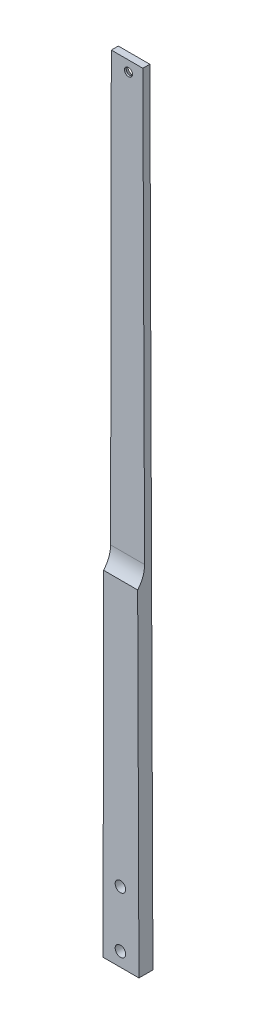
SolidWorks part; units mm, degrees
material "6061-T6 (SS)"
ref_plane "XY" through (0, 0, 0) normal (0, 0, 1) x (1, 0, 0)
ref_plane "XZ" through (0, 0, 0) normal (0, 1, 0) x (1, 0, 0)
ref_plane "YZ" through (0, 0, 0) normal (1, 0, 0) x (0, 0, -1)
ref_axis "X" through (-34.925, 0, 0) along (1, 0, 0)
ref_axis "Y" through (0, -53.3373, 0) along (0, 1, 0)
ref_axis "Z" through (0, 0, 6.6675) along (0, 0, -1)
sketch "Sketch1" plane through (0, 0, 0) normal (0, 0, 1) x (1, 0, 0)
  line L0 (-5.3354, 399.996) -> (10.3597, 399.996)
  line B0 (9.0464, 399.996) -> (-5.2871, 399.996)
  arc B1 (10.4977, 29.9643) -> (-5.8638, 31.2038) centre (0, 0) ccw
  spline B2 degree 3 poles (-5.2871, 399.996) (-5.392, 338.6022) (-5.5295, 254.0955) (-5.7181, 131.1648) (-5.8086, 69.6278) (-5.8638, 31.2038) knots 0 0 0 0 0.499418 0.687434 1 1 1 1
  spline B3 degree 3 poles (10.4977, 29.9643) (10.3579, 67.799) (10.0202, 157.8026) (9.6677, 247.8061) (9.323, 333.3153) (9.1861, 366.6557) (9.0464, 399.996) knots 0 0 0 0 0.306741 0.729696 0.729696 1 1 1 1
sketch_block_instance "Block2-3"
sketch_block "Block2"
sketch "Sketch2" plane through (0, 0, 0) normal (0, 0, 1) x (1, 0, 0)
  line L5 (-5.3354, 399.996) -> (10.3597, 399.996) construction
  line L6 (-5.2871, 399.996) -> (9.0464, 399.996)
  arc A1 (11.1829, 29.7154) -> (-6.1429, 31.1501) centre (0, 0) ccw construction
  arc A2 (10.4977, 29.9643) -> (-5.8638, 31.2038) centre (0, 0) ccw construction
  arc A3 (10.4977, 29.9643) -> (-5.8638, 31.2038) centre (0, 0) ccw
  spline S2 degree 3 poles (23.5275, -2969.9802) (16.0548, -1932.1789) (13.9359, -842.1823) (9.6677, 247.8061) (5.2912, 1333.2834) (-1.242, 2366.5824) (-18.9106, 3399.8182) knots -8.107291 -8.107291 -8.107291 -8.107291 0.306741 0.729696 0.729696 9.107159 9.107159 9.107159 9.107159 only from (10.4977, 29.9643) to (9.0464, 399.996) construction
  spline S3 degree 3 poles (7.1386, 3399.9286) (-1.0288, 2338.5658) (-3.9953, 1254.0783) (-7.2523, -868.8146) (-7.7134, -1930.3327) (-10.8836, -2968.7314) knots -8.134522 -8.134522 -8.134522 -8.134522 0.499418 0.687434 9.134495 9.134495 9.134495 9.134495 only from (-5.2871, 399.996) to (-5.8638, 31.2038) construction
  spline S8 degree 3 poles (10.4977, 29.9643) (10.3579, 67.799) (10.0202, 157.8026) (9.6677, 247.8061) (9.323, 333.3153) (9.1861, 366.6557) (9.0464, 399.996) knots 0 0 0 0 0.306741 0.729696 0.729696 1 1 1 1
  spline S9 degree 3 poles (-5.2871, 399.996) (-5.392, 338.6022) (-5.5295, 254.0955) (-5.7181, 131.1648) (-5.8086, 69.6278) (-5.8638, 31.2038) knots 0 0 0 0 0.499418 0.687434 1 1 1 1
  point P0 (0, 0)
extrude "Boss-Extrude1" add sketch "Sketch2" along normal blind 6.35
sketch "Sketch3" plane through (0, 0, 0) normal (0, 0, 1) x (1, 0, 0)
  line L0 (0, 0) -> (2.032, 0) construction
  line L1 (-9.398, 0) -> (13.462, 0)
  line L2 (-9.398, 0) -> (-9.398, 44.45)
  line L3 (-9.398, 44.45) -> (13.462, 44.45)
  line L4 (13.462, 0) -> (13.462, 44.45)
  line L9 (2.032, 0) -> (2.032, 44.45) construction
  line L11 (13.462, 44.45) -> (-9.398, 44.45) construction
  circle A0 centre (0, 0) radius 31.75 construction
  dimension "D1" = 63.5
  dimension "D2" = 44.45
  dimension "D3" = 2.032
  dimension "D6" = 22.86
extrude "Cut-Extrude2" cut sketch "Sketch3" against normal through all and the other way through all
hole_wizard "3/16 (0.1875) Dowel Hole1" positions "Sketch4" profile "Sketch5" hole size "3/16" standard "ANSI Inch"
sketch "Sketch4" plane through (0, 0, 6.35) normal (0, 0, 1) x (1, 0, 0)
  line L0 (2.032, 44.45) -> (2.032, 50.8) construction
  line L2 (2.032, 50.8) -> (2.032, 76.2) construction
  line L4 (10.4441, 44.45) -> (-5.8447, 44.45) construction
  point P0 (2.032, 50.8)
  point P2 (2.032, 76.2)
  dimension "D1" = 6.35
  dimension "D2" = 25.4
  dimension "D3" = 2.032
sketch "Sketch5" plane through (2.032, 50.8, 6.35) normal (1, 0, 0) x (0, -1, 0)
  line L0 (0, 0) -> (0, 12.0988)
  line L1 (0, 12.0988) -> (2.3812, 10.668)
  line L2 (2.3812, 10.668) -> (2.3812, 0)
  line L5 (2.3812, 0) -> (0, 0)
  line L10 (0, 12.0988) -> (-2.3813, 10.668) construction
  line L11 (0, -6.35) -> (0, 107.95) construction
  dimension "Hole Dia." = 4.7625
  dimension "Hole Depth" = 10.668
  dimension "Drill Angle" = 118
hole_wizard "CSK for #6 Flat Head Socket Cap Screw1" positions "Sketch6" profile "Sketch7" countersink size "#6" standard "ANSI Inch" end condition through all
sketch "Sketch6" plane through (0, 0, 0) normal (0, 0, -1) x (-1, 0, 0)
  line L0 (-2.5122, 395.2335) -> (-2.5122, 399.996) construction
  line L1 (5.3354, 399.996) -> (-10.3597, 399.996) construction
  point P0 (-2.5122, 395.2335)
  dimension "D1" = 4.7625
sketch "Sketch7" plane through (2.5122, 395.2335, 0) normal (1, 0, 0) x (0, 1, 0)
  line L0 (0, 0) -> (0, 6.35)
  line L1 (0, 6.35) -> (1.8288, 6.35)
  line L2 (1.8288, 6.35) -> (1.8288, 2.3814)
  line L3 (1.8288, 2.3814) -> (3.8989, 0)
  line L5 (3.8989, 0) -> (0, 0)
  line L6 (-1.8288, 2.3814) -> (-3.8989, 0) construction
  line L11 (0, -6.35) -> (0, 107.95) construction
  dimension "Thru Hole Dia." = 3.6576
  dimension "Thru Hole Depth" = 6.35
  dimension "Near C'Sink Dia." = 7.7978
  dimension "Near C'Sink Angle" = 82
sketch "Sketch8" plane through (0, 0, 6.35) normal (0, 0, 1) x (1, 0, 0)
  line L0 (-5.3354, 399.996) -> (10.3597, 399.996) construction
  line L1 (-35.5509, 399.996) -> (52.4162, 399.996)
  line L2 (-35.5509, 399.996) -> (-35.5509, 196.796)
  line L3 (-35.5509, 196.796) -> (52.4162, 196.796)
  line L4 (52.4162, 399.996) -> (52.4162, 196.796)
  dimension "D1" = 203.2
extrude "Cut-Extrude3" cut sketch "Sketch8" against normal blind 3.175
fillet "Fillet1" radius 12.7 1 edges at (2.1243, 196.796, 3.175)
